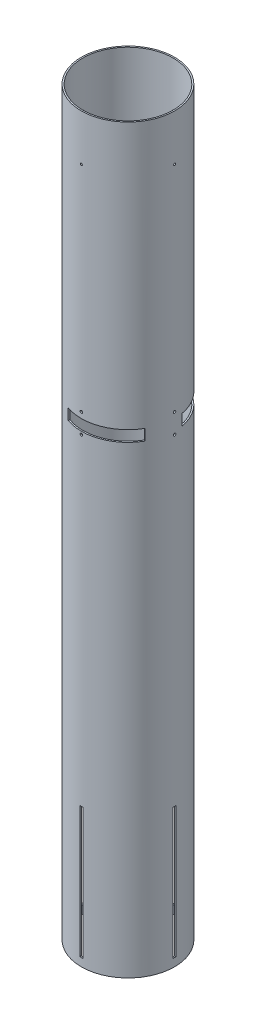
SolidWorks part; units mm, degrees
material "A-Glass Fiber"
ref_plane "Front Plane" through (0, 0, 0) normal (0, 0, 1) x (1, 0, 0)
ref_plane "Top Plane" through (0, 0, 0) normal (0, 1, 0) x (1, 0, 0)
ref_plane "Right Plane" through (0, 0, 0) normal (1, 0, 0) x (0, 0, -1)
sketch "Sketch1" plane through (0, 0, 0) normal (0, 1, 0) x (1, 0, 0)
  circle A0 centre (0, 0) radius 49.53
  circle A1 centre (0, 0) radius 51.1048
  dimension "D1" = 99.06
  dimension "D2" = 102.2096
extrude "Boss-Extrude1" add sketch "Sketch1" along normal blind 812.8
ref_plane "Plane1" through (0, 0, 0) normal (0.7071, 0, 0.7071) x (0.7071, 0, -0.7071)
ref_axis "Axis1" through (0, 812.8, 0) along (0, -1, 0)
sketch "Sketch2" plane through (0, 0, 0) normal (1, 0, 0) x (0, 0, -1)
  line L0 (0, 0) -> (0, 8.89)
  line L1 (1.5875, 8.89) -> (-1.5875, 8.89)
  line L2 (1.5875, 8.89) -> (1.5875, 152.4)
  line L3 (1.5875, 152.4) -> (-1.5875, 152.4)
  line L4 (-1.5875, 8.89) -> (-1.5875, 152.4)
  line L5 (1.5875, 8.89) -> (-1.5875, 152.4) construction
  line L6 (1.5875, 152.4) -> (-1.5875, 8.89) construction
  line L7 (51.1048, 812.8) -> (-51.1048, 812.8) construction
  line L8 (51.1048, 812.8) -> (-51.1048, 812.8)
  line L9 (0, 812.8) -> (0, 527.05)
  line L10 (-51.1048, 0) -> (51.1048, 0) construction
  circle A0 centre (0, 527.05) radius 1.3525
  point P0 (0, 80.645)
  dimension "D4" = 2.7051
  dimension "D1" = 3.175
  dimension "D5" = 527.05
  dimension "D3" = 152.4
  dimension "D2" = 8.89
extrude "Cut-Extrude1" cut sketch "Sketch2" against normal through all contours L4 L1 L2 L3 region at (0, 80.645, 0)
pattern_circular "CirPattern1" count 4 over 360 about axis through (0, 0, 0) along (0, 1, 0) of "Cut-Extrude1" reverse direction yes
extrude "Cut-Extrude2" cut sketch "Sketch2<3>" against normal through all contours A0 region at (0, 526.1207, 0.9293)
sketch "Sketch2<3>" plane through (0, 0, 0) normal (1, 0, 0) x (0, 0, -1) same geometry as "Sketch2"
pattern_circular "CirPattern2" count 4 over 360 about axis through (0, 812.8, 0) along (0, -1, 0) of "Cut-Extrude2"
sketch "Sketch3" plane through (0, 0, 0) normal (0.7071, 0, 0.7071) x (0.7071, 0, -0.7071)
  line L0 (0, 0) -> (0, 127) construction
  circle A0 centre (0, 127) radius 3.175
  dimension "D1" = 6.35
  dimension "D2" = 127
extrude "Cut-Extrude3" cut sketch "Sketch3" against normal through all
sketch "Sketch7" plane through (0, 0, 0) normal (0, 1, 0) x (1, 0, 0)
  line L0 (0, 0) -> (-44.2581, -25.5524)
  line L1 (0, 0) -> (0, 93.232) construction
  line L2 (0, 0) -> (-32.8495, 39.1485)
  line L3 (-51.1048, 0) -> (0, 0) construction
  arc A0 (-51.0869, 1.3525) -> (-51.0869, -1.3525) centre (0, 0) ccw construction
  circle A1 centre (0, 0) radius 49.53 construction
  circle A2 centre (0, 0) radius 51.1048
  circle A3 centre (0, 0) radius 51.1048
  circle A4 centre (0, 0) radius 49.53
  circle A5 centre (0, 0) radius 51.1048 construction
  arc A6 (1.3526, 51.0869) -> (-1.3525, 51.0869) centre (0, 0) ccw construction
  arc A7 (-51.0869, 1.3525) -> (-51.0869, -1.3525) centre (0, 0) ccw
  arc A8 (1.3526, 51.0869) -> (-1.3525, 51.0869) centre (0, 0) ccw
  dimension "D1" = 80
  dimension "D3" = 30
  dimension "D2" = 0
extrude "Cut-Extrude4" cut sketch "Sketch7" against normal blind 12.065 from offset 520.7 contours A4 A3 L0 region at (-43.9137, 0, 24.5741)
pattern_circular "CirPattern3" count 3 over 360 about axis through (0, 812.8, 0) along (0, -1, 0) of "Cut-Extrude4"
pattern_linear "LPattern1" count 2 spacing 21.6916 along (0, -1, 0) of "CirPattern2"
sketch "Sketch8" plane through (0, 0, 0) normal (0, 0, 1) x (1, 0, 0)
  line L0 (49.53, 812.8) -> (-49.53, 812.8) construction
  circle A0 centre (0, 762) radius 1.0922
  point P4 (0, 0)
  dimension "D1" = 2.1844
  dimension "D2" = 50.8
extrude "Cut-Extrude5" cut sketch "Sketch8" against normal through all
pattern_circular "CirPattern4" count 4 over 360 about axis through (0, 812.8, 0) along (0, -1, 0) of "Cut-Extrude5"
equation "\"D1@Boss-Extrude1\" = \"Aft_Section_Length\""
equation "\"AB_Coupler_OD_Length\"= 1in"
equation "\"AB_Coupling_Section_Length\"= 0.375in"
equation "\"AB_Coupler_Length\"= \"AB_Coupler_OD_Length\" + \"AB_Coupling_Section_Length\" * 2"
equation "\"AB_Coupler_Num_Screws\"= 4"
equation "\"AB_Coupling_Screw_Diameter\"= 0.1065in"
equation "\"Aft_Section_Length\" = 32in"
equation "\"D4@Sketch2\"=\"AB_Coupling_Screw_Diameter\""
equation "\"D1@CirPattern2\"=\"AB_Coupler_Num_Screws\""
equation "\"Rail_Nut_From_Bottom\"= 5in"
equation "\"Rail_Nut_Diam\"= 0.25in"
equation "\"D1@Sketch3\"=\"Rail_Nut_Diam\""
equation "\"D2@Sketch3\"=\"Rail_Nut_From_Bottom\""
equation "\"AB_BKHD_Thickness\"= 0.375in"
equation "\"AB_Mount_From_Bottom\"= 20.75in"
equation "\"Cutout_Angle\" = 60"
equation "\"Motor_OD\" = 54.4mm"
equation "\"Motor_Length\" = 401mm"
equation "\"Mid_Coupler_Length\" = 12in"
equation "\"AB_Paddle_Height\" = 0.375in"
equation "\"Num_Cutouts\" = 4"
equation "\"AB_Coupler_OD\"= 4.024in"
equation "\"AB_Coupler_ID\"= 3.7in"
equation "\"AB_Coupler_Surface_Diameter\"= 3.899in"
equation "\"AB_Central_Bushing_Length\" = 0.75in"
equation "\"Lead_Screw_Dist\" = 2in"
equation "\"Lead_Screw_Diam\" = 0.375in"
equation "\"Lead_Screw_Length\" = \"Mid_Coupler_Length\" + 2*0.375in + 2*0.5in"
equation "\"Paddle_Pin_Offset\" = 0.25in"
equation "\"Paddle_Pin_Radius\" = 2.25*2/3in"
equation "\"Paddle_Gear_OD\" = 3.2in"
equation "\"Fwd_BKHD_From_Top\" = 18in"
equation "\"Body_Tube_OD\"= 4.024in"
equation "\"Body_Tube_ID\"= 3.90in"
equation "\"Coupler_OD\" = 3.899in"
equation "\"Coupler_ID\" = 3.755in"
equation "\"Fwd_Section_Length\" = 20in"
equation "\"Mid_Section_Length\" = 4in"
equation "\"Aft_Upper_Tube_Length\" = 10in"
equation "\"Aft_Lower_Tube_Length\" = 18in"
equation "\"Nosecone_Coupler_Length\" = 5in"
equation "\"Avionics_Bulkhead_Thickness\" = 0.25in"
equation "\"Avionics_Bulkhead_Lip\" = 0.125in"
equation "\"Avionics_Board_Length\" = \"Mid_Coupler_Length\" - 2*\"Avionics_Bulkhead_Lip\""
equation "\"Lead_Screw_Hole_Diam\" = 0.386in"
equation "\"Centering_Ring_Cutout_Dia\"= 1in"
equation "\"D2@Sketch1\"=\"Body_Tube_OD\""
equation "\"D1@Sketch1\"=\"Body_Tube_ID\""
equation "\"D5@Sketch2\"=\"AB_Mount_From_Bottom\""
equation "\"D19@Cut-Extrude4\"=\"AB_Mount_From_Bottom\"-0.25"
